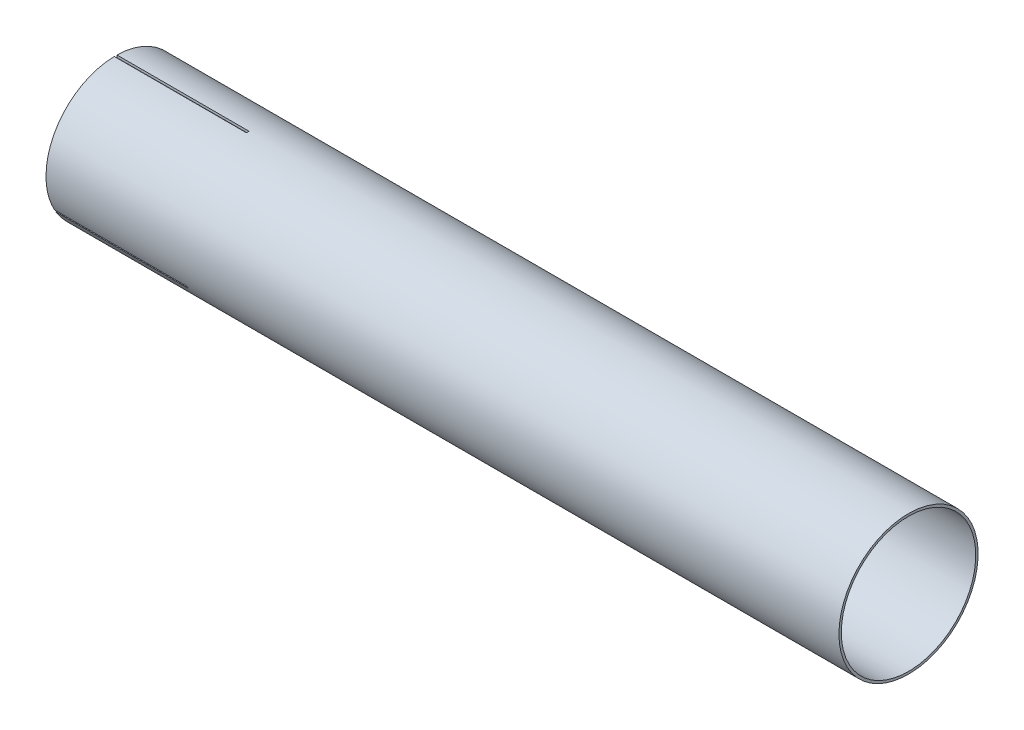
SolidWorks part; units mm, degrees
ref_plane "Plan de face" through (0, 0, 0) normal (0, 0, 1) x (1, 0, 0)
ref_plane "Plan de dessus" through (0, 0, 0) normal (0, 1, 0) x (1, 0, 0)
ref_plane "Plan de droite" through (0, 0, 0) normal (1, 0, 0) x (0, 0, -1)
sketch "Esquisse1" plane through (0, 0, 0) normal (0, 0, 1) x (1, 0, 0)
  line L0 (0, 0) -> (0, 79) construction
  line L1 (0, 0) -> (142.5133, 0) construction
  line L2 (0, 79) -> (900, 79)
  line L3 (0, 79) -> (0, -79) construction
  line L4 (0, 76.29) -> (900, 76.29)
  line L5 (900, 79) -> (900, 76.29)
  line L6 (0, -79) -> (900, -79) construction
  line L7 (0, 79) -> (0, 76.29)
  dimension "D1" = 158
  dimension "D2" = 152.58
  dimension "D3" = 900
revolve "Révolution1" add sketch "Esquisse1" angle 360 about L1
sketch "Esquisse2" plane through (0, 0, 0) normal (0, 1, 0) x (1, 0, 0)
  line L0 (0, 79) -> (0, -79) construction
  line L1 (0, -1.5) -> (150, -1.5)
  line L2 (0, -1.5) -> (0, 1.5)
  line L3 (0, 1.5) -> (150, 1.5)
  line L4 (150, -1.5) -> (150, 1.5)
  dimension "D1" = 3
  dimension "D2" = 150
extrude "Enlèv. mat.-Extru.1" cut sketch "Esquisse2" along normal through all
pattern_circular "Répétition circulaire1" count 3 over 240 about axis through (900, 0, 0) along (-1, 0, 0) of "Enlèv. mat.-Extru.1"
